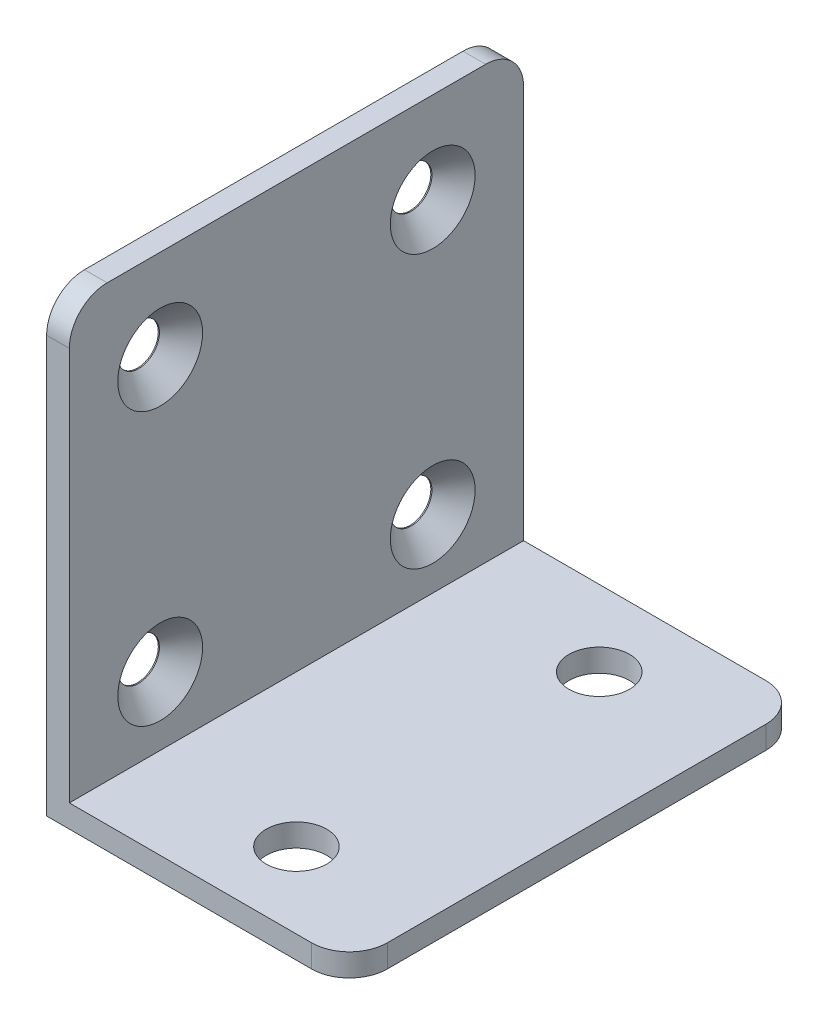
SolidWorks part; units mm, degrees
ref_plane "Płaszczyzna przednia" through (0, 0, 0) normal (0, 0, 1) x (1, 0, 0)
ref_plane "Płaszczyzna górna" through (0, 0, 0) normal (0, 1, 0) x (1, 0, 0)
ref_plane "Płaszczyzna prawa" through (0, 0, 0) normal (1, 0, 0) x (0, 0, -1)
sketch "Szkic1" plane through (0, 0, 0) normal (0, 0, 1) x (1, 0, 0)
  line L1 (-20, -30) -> (20, -30)
  line L2 (-20, -30) -> (-20, 30)
  line L3 (-20, 30) -> (20, 30)
  line L4 (20, -30) -> (20, 30)
  line L5 (-20, -30) -> (20, 30) construction
  line L6 (-20, 30) -> (20, -30) construction
  point P0 (0, 0)
  dimension "D1" = 40
  dimension "D2" = 60
extrude "Dodanie-wyciągnięcie1" add sketch "Szkic1" along normal blind 30 and the other way blind 30
sketch "Szkic2" plane through (0, 0, 30) normal (0, 0, 1) x (1, 0, 0)
  line L0 (-20, 30) -> (-20, -30) construction
  line L1 (20, 30) -> (-17, 30)
  line L2 (20, 30) -> (20, -27)
  line L3 (20, -27) -> (-17, -27)
  line L4 (-17, 30) -> (-17, -27)
  line L5 (-20, -30) -> (20, -30) construction
  dimension "D1" = 3
  dimension "D2" = 3
extrude "Wytnij-wyciągnięcie1" cut sketch "Szkic2" against normal through all
sketch "Szkic3" plane through (0, -30, 0) normal (0, -1, 0) x (-1, 0, 0)
  line L1 (-25.5595, 0) -> (24.7788, 0) construction
  circle A0 centre (-3, -20) radius 4
  circle A2 centre (-3, 20) radius 4
  dimension "D1" = 8
  dimension "D3" = 20
  dimension "D4" = 40
extrude "Wytnij-wyciągnięcie2" cut sketch "Szkic3" against normal blind 40
sketch "Szkic4" plane through (-17, 0, 0) normal (1, 0, 0) x (0, 0, -1)
  line L1 (-18, -18) -> (18, -18)
  line L2 (-18, -18) -> (-18, 18)
  line L3 (-18, 18) -> (18, 18)
  line L4 (18, -18) -> (18, 18)
  line L5 (-18, -18) -> (18, 18) construction
  line L6 (-18, 18) -> (18, -18) construction
  point P0 (0, 0)
  dimension "D1" = 36
  dimension "D2" = 36
hole_wizard "Pogłębienie stożkowe pod M5 Wkręt z łbem stożkowym płaskim1" positions "Szkic5" profile "Szkic6" countersink size "M5" standard "ISO"
sketch "Szkic5" plane through (-17, 0, 0) normal (1, 0, 0) x (0, 0, -1)
  point P0 (-18, 18)
  point P3 (18, 18)
  point P6 (18, -18)
  point P9 (-18, -18)
sketch "Szkic6" plane through (-17, 18, 18) normal (0, 1, 0) x (0, 0, -1)
  line L0 (0, 0) -> (0, 11.6524)
  line L1 (0, 11.6524) -> (2.75, 10)
  line L2 (2.75, 10) -> (2.75, 2.85)
  line L3 (2.75, 2.85) -> (5.6, 0)
  line L5 (5.6, 0) -> (0, 0)
  line L6 (-2.75, 2.85) -> (-5.6, 0) construction
  line L10 (0, 11.6524) -> (-2.75, 10) construction
  line L11 (0, -6.35) -> (0, 107.95) construction
  dimension "Średnica otworu" = 5.5
  dimension "Głębokośc otworu" = 10
  dimension "Średnica zewnętrznego pogłębienia stożkowego" = 11.2
  dimension "Kąt zewnętrznego pogłębienia stożkowego" = 90
  dimension "Kąt wiertła" = 118
fillet "Zaokrąglenie1" radius 5 4 edges at (-18.5, 30, -30) (-18.5, 30, 30) (20, -28.5, -30) (20, -28.5, 30)
